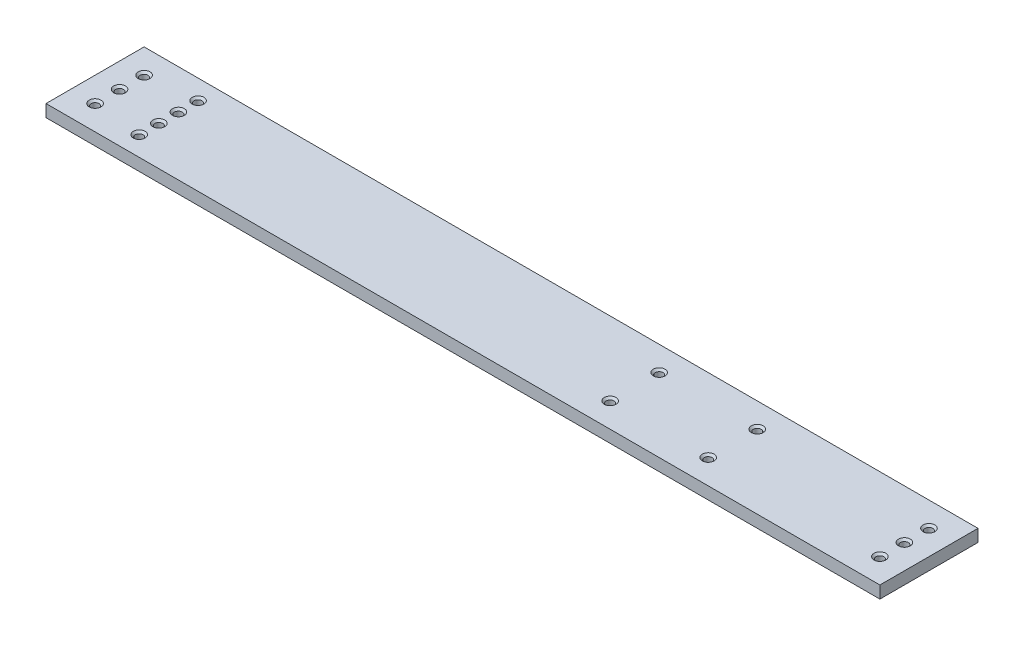
SolidWorks part; units mm, degrees
material "6061-T6 (SS)"
ref_plane "Front" through (0, 0, 0) normal (0, 0, 1) x (1, 0, 0)
ref_plane "Top" through (0, 0, 0) normal (0, 1, 0) x (1, 0, 0)
ref_plane "Right" through (0, 0, 0) normal (1, 0, 0) x (0, 0, -1)
sketch "Sketch1" plane through (0, 0, 0) normal (0, 1, 0) x (1, 0, 0)
  line L1 (-215.9, -25.4) -> (215.9, -25.4)
  line L2 (-215.9, -25.4) -> (-215.9, 25.4)
  line L3 (-215.9, 25.4) -> (215.9, 25.4)
  line L4 (215.9, -25.4) -> (215.9, 25.4)
  line L5 (-215.9, -25.4) -> (215.9, 25.4) construction
  line L6 (-215.9, 25.4) -> (215.9, -25.4) construction
  point P0 (0, 0)
  dimension "D1" = 50.8
  dimension "D2" = 431.8
extrude "Boss-Extrude1" add sketch "Sketch1" along normal blind 6.35
hole_wizard "#10-32 Tapped Hole1" positions "Sketch2" profile "Sketch4" tap size "#10-32" standard "ANSI Inch" end condition through all
sketch "Sketch2" plane through (0, 6.35, 0) normal (0, 1, 0) x (1, 0, 0)
  line L1 (-203.2, 25.4) -> (-203.2, 12.7) construction
  line L2 (215.9, 25.4) -> (-215.9, 25.4) construction
  line L3 (-203.2, 12.7) -> (-203.2, 0) construction
  line L4 (-203.2, 0) -> (-203.2, -12.7) construction
  line L5 (-203.2, -12.7) -> (-203.2, -25.4) construction
  line L6 (-215.9, -25.4) -> (215.9, -25.4) construction
  line L8 (-215.9, 25.4) -> (-215.9, -25.4) construction
  line L9 (-203.2, 0) -> (-215.9, 0) construction
  line L11 (203.2, 0) -> (215.9, 0) construction
  line L12 (215.9, -25.4) -> (215.9, 25.4) construction
  line L15 (63.5, 12.7) -> (63.5, 25.4) construction
  line L17 (63.5, -12.7) -> (63.5, -25.4) construction
  line L18 (-177.8, -25.4) -> (-177.8, -15.24) construction
  line L20 (-177.8, 5.08) -> (-177.8, 15.24) construction
  line L21 (-177.8, 15.24) -> (-177.8, 25.4) construction
  line L22 (-177.8, 5.08) -> (-177.8, -5.08) construction
  line L23 (-177.8, -5.08) -> (-177.8, -15.24) construction
  point P0 (-203.2, 12.7)
  point P2 (-203.2, 0)
  point P4 (-203.2, -12.7)
  point P6 (203.2, 12.7)
  point P8 (203.2, 0)
  point P10 (203.2, -12.7)
  point P64 (63.5, 12.7)
  point P66 (114.3, 12.7)
  point P68 (63.5, -12.7)
  point P70 (114.3, -12.7)
  point P92 (-177.8, 15.24)
  point P94 (-177.8, 5.08)
  point P102 (-177.8, -15.24)
  point P127 (-177.8, -5.08)
  point P137 (-182.2586, -5.08)
  point P138 (-182.2586, -15.24)
  point P139 (-170.8567, 0)
  point P140 (-179.4734, 15.24)
  point P141 (-178.3419, 5.08)
  point P142 (-178.9512, -5.08)
  point P143 (-179.6475, -15.24)
  dimension "D1" = 12.7
  dimension "D2" = 50.8
  dimension "D3" = 25.4
  dimension "D4" = 101.6
  dimension "D5" = 38.1
sketch "Sketch4" plane through (-203.2, 6.35, -12.7) normal (1, 0, 0) x (0, 0, 1)
  line L0 (0, 0) -> (0, 6.35)
  line L1 (0, 6.35) -> (2.0193, 6.35)
  line L2 (2.0193, 6.35) -> (2.0193, 1.0287)
  line L3 (2.0193, 1.0287) -> (3.048, 0)
  line L5 (3.048, 0) -> (0, 0)
  line L6 (-2.0193, 1.0287) -> (-3.048, 0) construction
  line L11 (0, -6.35) -> (0, 107.95) construction
  dimension "Thru Tap Drill Dia." = 4.0386
  dimension "Thru Tap Drill Depth" = 6.35
  dimension "Near C'Sink Dia." = 6.096
  dimension "Near C'Sink Angle" = 90
cosmetic thread "Hole Thread3"
cosmetic thread "Hole Thread4"
cosmetic thread "Hole Thread5"
cosmetic thread "Hole Thread6"
cosmetic thread "Hole Thread7"
cosmetic thread "Hole Thread9"
cosmetic thread "Hole Thread10"
cosmetic thread "Hole Thread11"
cosmetic thread "Hole Thread12"
cosmetic thread "Hole Thread13"
cosmetic thread "Hole Thread15"
cosmetic thread "Hole Thread16"
cosmetic thread "Hole Thread17"
cosmetic thread "Hole Thread18"
